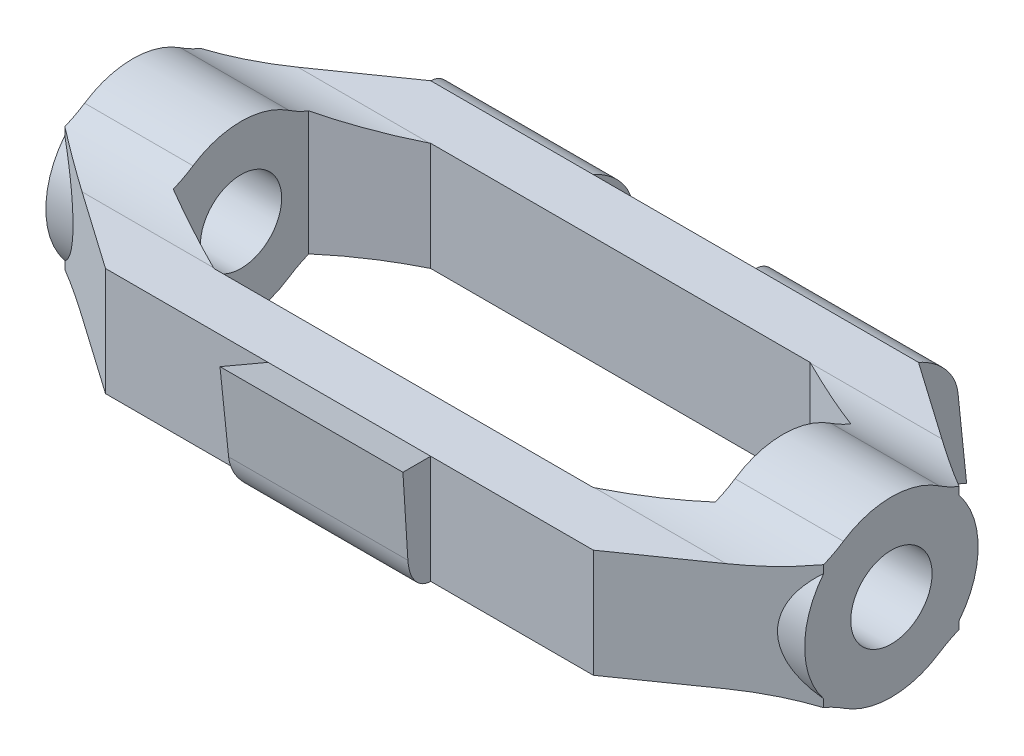
SolidWorks part; units mm, degrees
material "AISI 4340 Aço, normalizado"
ref_plane "Plano frontal" through (0, 0, 0) normal (0, 0, 1) x (1, 0, 0)
ref_plane "Plano superior" through (0, 0, 0) normal (0, 1, 0) x (1, 0, 0)
ref_plane "Plano direito" through (0, 0, 0) normal (1, 0, 0) x (0, 0, -1)
ref_plane "Plano1" through (-50, 0, 0) normal (1, 0, 0) x (0, 0, -1)
sketch "Esboço1" plane through (0, 0, 0) normal (0, 1, 0) x (1, 0, 0)
  line L0 (0, 0) -> (0, -28.2729) construction
  line L1 (-45, 30) -> (45, 30)
  line L2 (-45, -30) -> (45, -30)
  line L3 (-70, 12.5) -> (-70, -12.5) construction
  line L4 (-70, -12.5) -> (-45, -30)
  line L5 (-70, 12.5) -> (-45, 30)
  line L6 (-50, 12.5) -> (-70, 12.5)
  line L7 (-70, -12.5) -> (-50, -12.5)
  line L8 (-50, -12.5) -> (-35, -20)
  line L9 (-50, 12.5) -> (-35, 20)
  line L10 (-35, 20) -> (35, 20)
  line L11 (-35, -20) -> (35, -20)
  line L12 (70, 12.5) -> (70, -12.5) construction
  line L13 (50, 12.5) -> (35, 20)
  line L14 (50, -12.5) -> (35, -20)
  line L16 (-50, -12.5) -> (-70, -12.5)
  line L17 (45, -30) -> (70, -12.5)
  line L18 (45, 30) -> (70, 12.5)
  line L19 (70, 12.5) -> (50, 12.5)
  line L20 (70, -12.5) -> (50, -12.5)
  line L21 (39.3758, 0) -> (-39.3758, 0) construction
  point P8 (0, 30)
  point P9 (0, -30)
  point P13 (-70, 0)
  point P22 (70, 0)
  point P27 (0, 0)
  point P29 (0, -20)
  point P30 (0, 20)
  dimension "D1" = 30
  dimension "D4" = 90
  dimension "D5" = 10
  dimension "D6" = 20
  dimension "D7" = 70
  dimension "D8" = 15
extrude "Ressalto-extrusão1" add sketch "Esboço1" along normal mid plane 20 contours L17 L20 L14 L11 L8 L7 L4 L2 | L19 L18 L1 L5 L6 L9 L10 L13 region at (0, 0, -22.7424) region at (0, 0, 22.7424)
sketch "Esboço2" plane through (-50, 0, 0) normal (1, 0, 0) x (0, 0, -1)
  line L0 (12.5, 10) -> (-12.5, 10) construction
  line L1 (12.5, -10) -> (-12.5, -10) construction
  circle A0 centre (0, 0) radius 7.5
  circle A1 centre (0, 0) radius 16.0078
  dimension "D1" = 15
extrude "Ressalto-extrusão2" add sketch "Esboço2" against normal blind 20
mirror "Espelhar1" about plane through (0, 0, 0) normal (1, 0, 0) of "Ressalto-extrusão2"
fillet "Filete1" radius 20 8 edges at (-60, 10, -12.5) (-60, -10, 12.5) (-60, -10, -12.5) (-60, 10, 12.5) (60, 10, 12.5) (60, -10, 12.5) (60, -10, -12.5) (60, 10, -12.5)
sketch "Esboço3" plane through (0, 0, 30) normal (0, 0, 1) x (1, 0, 0)
  line L3 (-15, -10) -> (15, -10)
  line L4 (-45, -10) -> (45, -10) construction
  line L6 (-15, 10) -> (-15, -10)
  line L8 (15, 10) -> (15, -10)
  line L9 (15, 10) -> (-15, 10)
  point P0 (0, -10)
  point P1 (0, 10)
  point P2 (0, 0)
  point P5 (0, 0)
  point P12 (0, 0)
  point P15 (-15, 0)
  point P18 (15, 0)
  dimension "D2" = 30
sketch "Esboço4" plane through (0, 0, -30) normal (0, 0, -1) x (-1, 0, 0)
  line L0 (45, -10) -> (-45, -10) construction
  line L1 (-45, 10) -> (-15, 10)
  line L2 (-45, 10) -> (-45, -10)
  line L3 (-45, -10) -> (-15, -10)
  line L4 (-15, 10) -> (-15, -10)
  line L5 (0, 0) -> (0, -39.7615) construction
  line L6 (15, 10) -> (15, -10)
  line L7 (45, -10) -> (15, -10)
  line L8 (45, 10) -> (45, -10)
  line L9 (45, 10) -> (15, 10)
  dimension "D1" = 30
  dimension "D2" = 30
extrude "Ressalto-extrusão3" add sketch "Esboço3" along normal blind 7 draft 15 draft outward yes
sketch "Esboço8" plane through (0, 0, 0) normal (1, 0, 0) x (0, 0, -1)
  line L0 (-37, 0) -> (-36, 0) construction
  line L1 (-37, -11.8756) -> (-37, 11.8756) construction
  line L2 (200000, 0) -> (-200028.2729, 0) construction
  line L3 (-37, 11.8756) -> (-35.0441, -11.3516)
  line L4 (-37, -11.8756) -> (-30, -10) construction
  line L5 (-35.0441, -11.3516) -> (-37, -11.8756)
  line L6 (-37, -11.8756) -> (-37, 11.8756)
  dimension "D1" = 1
extrude "Ressalto-extrusão4" add sketch "Esboço4" along normal blind 7 draft 15 draft outward yes
extrude "Corte-extrusão1" cut sketch "Esboço8" against normal mid plane 33.76
sketch "Esboço7" plane through (0, 0, 0) normal (1, 0, 0) x (0, 0, -1)
  line L0 (37, 0) -> (36, 0) construction
  line L2 (200000, 0) -> (-200028.2729, 0) construction
  line L5 (37, 11.8756) -> (37, -11.8756)
  line L6 (37, -11.8756) -> (35.0441, 11.3516)
  line L7 (37, 11.8756) -> (30, 10) construction
  line L8 (35.0441, 11.3516) -> (37, 11.8756)
  dimension "D1" = 1
extrude "Corte-extrusão2" cut sketch "Esboço7" against normal mid plane 93.76
fillet "Filete4" radius 8 3 edges at (0, -11.3516, 35.0441) (30, 11.3516, -35.0441) (-30, 11.3516, -35.0441)
